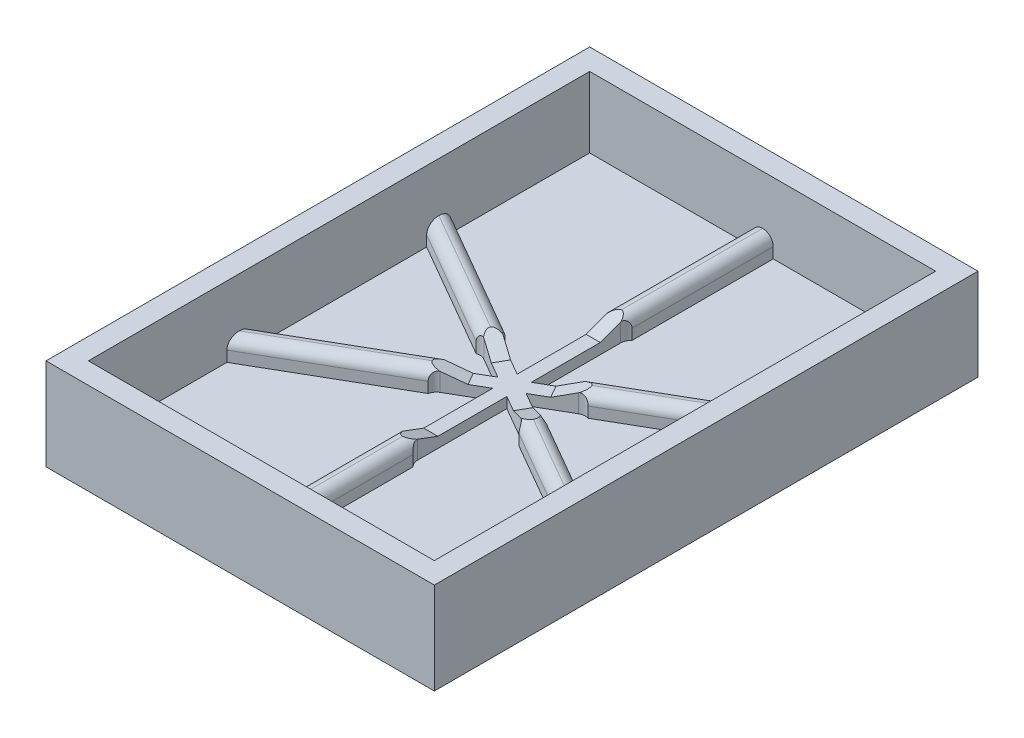
SolidWorks part; units mm, degrees
ref_plane "Plan de face" through (0, 0, 0) normal (0, 0, 1) x (1, 0, 0)
ref_plane "Plan de dessus" through (0, 0, 0) normal (0, 1, 0) x (1, 0, 0)
ref_plane "Plan de droite" through (0, 0, 0) normal (1, 0, 0) x (0, 0, -1)
sketch "Esquisse1" plane through (0, 0, 0) normal (0, 1, 0) x (1, 0, 0)
  line L1 (-27.5, -38.5) -> (27.5, -38.5)
  line L2 (-27.5, -38.5) -> (-27.5, 38.5)
  line L3 (-27.5, 38.5) -> (27.5, 38.5)
  line L4 (27.5, -38.5) -> (27.5, 38.5)
  line L5 (-27.5, -38.5) -> (27.5, 38.5) construction
  line L6 (-27.5, 38.5) -> (27.5, -38.5) construction
  point P0 (0, 0)
  dimension "D1" = 55
  dimension "D2" = 77
extrude "Boss.-Extru.1" add sketch "Esquisse1" along normal blind 3
sketch "Esquisse2" plane through (0, 3, 0) normal (0, 1, 0) x (1, 0, 0)
  line L0 (-24.5, 35.5) -> (-24.5, -35.5)
  line L1 (-27.5, 38.5) -> (27.5, 38.5)
  line L2 (-27.5, 38.5) -> (-27.5, -38.5)
  line L3 (-27.5, -38.5) -> (27.5, -38.5)
  line L4 (27.5, 38.5) -> (27.5, -38.5)
  line L5 (-24.5, -35.5) -> (24.5, -35.5)
  line L6 (24.5, 35.5) -> (24.5, -35.5)
  line L7 (-24.5, 35.5) -> (24.5, 35.5)
  dimension "D1" = 3
extrude "Boss.-Extru.2" add sketch "Esquisse2" along normal blind 10
sketch "Esquisse3" plane through (0, 3, 0) normal (0, 1, 0) x (1, 0, 0)
  line L0 (0, 35.5) -> (0, -35.5) construction
  line L1 (24.5, 35.5) -> (-24.5, 35.5) construction
  line L2 (-24.5, -35.5) -> (24.5, -35.5) construction
  line L3 (-24.5, 14.1451) -> (0, 0) construction
  line L4 (-24.5, 35.5) -> (-24.5, -35.5) construction
  line L5 (0, 0) -> (-24.5, 0) construction
  line L6 (-1, -35.5) -> (-1, -1.7321)
  line L7 (-1, -35.5) -> (1, -35.5)
  line L8 (-1, 35.5) -> (1, 35.5)
  line L9 (1, -35.5) -> (1, -1.7321)
  line L10 (-1, -35.5) -> (1, 35.5) construction
  line L11 (-1, 35.5) -> (1, -35.5) construction
  line L12 (25.4808, -15.866) -> (1, -1.7321)
  line L13 (25.4808, -15.866) -> (26.4808, -14.134)
  line L14 (-26.4808, 14.134) -> (-25.4808, 15.866)
  line L15 (26.4808, -14.134) -> (2, 0)
  line L16 (25.4808, -15.866) -> (-25.4808, 15.866) construction
  line L17 (-26.4808, 14.134) -> (26.4808, -14.134) construction
  line L18 (25.4808, 15.866) -> (26.4808, 14.134)
  line L19 (25.4808, 15.866) -> (1, 1.7321)
  line L20 (26.4808, 14.134) -> (2, 0)
  line L21 (-26.4808, -14.134) -> (-25.4808, -15.866)
  line L22 (-2, 0) -> (-26.4808, -14.134)
  line L23 (-2, 0) -> (-26.4808, 14.134)
  line L24 (-1, -1.7321) -> (-25.4808, -15.866)
  line L25 (-1, 1.7321) -> (-1, 35.5)
  line L26 (-1, 1.7321) -> (-25.4808, 15.866)
  line L27 (1, 1.7321) -> (1, 35.5)
  dimension "D1" = 30
  dimension "D2" = 2
  dimension "D3" = 1
  dimension "D4" = 1
  dimension "D5" = 60
extrude "Boss.-Extru.5" add sketch "Esquisse3" along normal blind 1.5
sketch "Esquisse4" plane through (0, 3, 0) normal (0, 1, 0) x (1, 0, 0)
  line L0 (1, 35.5) -> (-1, 35.5) construction
  line L1 (1.5, 35.5) -> (-1.5, 35.5)
  line L2 (0, 35.5) -> (0, 15.5)
  line L3 (1.5, 15.5) -> (-1.5, 15.5)
  line L4 (-1.5, 35.5) -> (-1.5, 15.5)
  line L5 (1.5, 35.5) -> (1.5, 15.5)
  line L6 (0, 0) -> (24.5, 0) construction
  line L7 (24.5, -35.5) -> (24.5, 35.5) construction
  line L8 (1.5, -35.5) -> (1.5, -15.5)
  line L9 (1.5, -35.5) -> (-1.5, -35.5)
  line L10 (-1.5, -35.5) -> (-1.5, -15.5)
  line L11 (1.5, -15.5) -> (-1.5, -15.5)
  line L12 (-24.5, 14.1451) -> (24.5, -14.1451) construction
  line L13 (-24.5, 15.2998) -> (-24.5, 12.9904) construction
  line L14 (24.5, -15.2998) -> (24.5, -12.9904) construction
  line L15 (24.5, -14.1451) -> (24.5, 14.1451) construction
  line L16 (24.5, 12.9904) -> (24.5, 15.2998) construction
  line L17 (24.5, 14.1451) -> (-24.5, -14.1451) construction
  line L18 (-24.5, -12.9904) -> (-24.5, -15.2998) construction
  line L19 (-24.5, -14.1451) -> (0, 0) construction
  line L20 (0, 0) -> (0, 8.3395) construction
  line L21 (-7.1795, 4.1451) -> (-25.5851, 14.7716)
  line L22 (-7.9295, 2.846) -> (-6.4295, 5.4441)
  line L23 (-26.3351, 13.4725) -> (-24.8351, 16.0706)
  line L24 (-6.4295, 5.4441) -> (-24.8351, 16.0706)
  line L25 (-7.9295, 2.846) -> (-26.3351, 13.4725)
  line L26 (-7.9295, -2.846) -> (-26.3351, -13.4725)
  line L27 (-7.9295, -2.846) -> (-6.4295, -5.4441)
  line L28 (-6.4295, -5.4441) -> (-24.8351, -16.0706)
  line L29 (-26.3351, -13.4725) -> (-24.8351, -16.0706)
  line L30 (7.9295, 2.846) -> (26.3351, 13.4725)
  line L31 (7.9295, 2.846) -> (6.4295, 5.4441)
  line L32 (6.4295, 5.4441) -> (24.8351, 16.0706)
  line L33 (26.3351, 13.4725) -> (24.8351, 16.0706)
  line L34 (7.9295, -2.846) -> (6.4295, -5.4441)
  line L35 (6.4295, -5.4441) -> (24.8351, -16.0706)
  line L36 (26.3351, -13.4725) -> (24.8351, -16.0706)
  line L37 (7.9295, -2.846) -> (26.3351, -13.4725)
  dimension "D1" = 20
  dimension "D2" = 3
  dimension "D3" = 20
  dimension "D4" = 3
extrude "Boss.-Extru.6" add sketch "Esquisse4" along normal blind 3 contours L26 L29 L28 L27 | L5 L3 L4 L1 | L22 L24 L23 L25 | L31 L32 L33 L30 | L35 L36 L37 L34 | L11 L10 L9 L8 region at (-16.3823, 3, 9.4583)
sketch "Esquisse5" plane through (1, 0, 0) normal (1, 0, 0) x (0, 0, -1)
  line L0 (15.5, 4.5) -> (15.5, 6)
  line L1 (15.5, 6) -> (11.5, 4.5)
  line L2 (1.7321, 4.5) -> (15.5, 4.5) construction
  line L3 (11.5, 4.5) -> (15.5, 4.5)
  line L4 (-15.5, 4.5) -> (-15.5, 6)
  line L5 (-15.5, 6) -> (-11.5, 4.5)
  line L6 (-15.5, 4.5) -> (-1.7321, 4.5) construction
  line L7 (-11.5, 4.5) -> (-15.5, 4.5)
  dimension "D1" = 1.5
  dimension "D2" = 4
  dimension "D3" = 4
  dimension "D4" = 1.5
extrude "Boss.-Extru.7" add sketch "Esquisse5" against normal blind 2
sketch "Esquisse6" plane through (0.5, 0, -0.866) normal (0.5, 0, -0.866) x (-0.866, 0, -0.5)
  line L0 (8.2902, 4.5) -> (8.2902, 6)
  line L1 (8.2902, 6) -> (4.2902, 4.5)
  line L2 (1.7321, 4.5) -> (8.2902, 4.5) construction
  line L3 (4.2902, 4.5) -> (8.2902, 4.5)
  line L4 (-8.2902, 4.5) -> (-8.2902, 6)
  line L5 (-8.2902, 6) -> (-4.2902, 4.5)
  line L6 (-8.2902, 4.5) -> (-1.7321, 4.5) construction
  line L7 (-4.2902, 4.5) -> (-8.2902, 4.5)
  dimension "D1" = 4
  dimension "D2" = 1.5
  dimension "D3" = 4
  dimension "D4" = 1.5
extrude "Boss.-Extru.8" add sketch "Esquisse6" against normal blind 2
sketch "Esquisse7" plane through (-0.5, 0, -0.866) normal (-0.5, 0, -0.866) x (-0.866, 0, 0.5)
  line L0 (8.2902, 4.5) -> (8.2902, 6)
  line L1 (8.2902, 6) -> (4.2902, 4.5)
  line L2 (1.7321, 4.5) -> (8.2902, 4.5) construction
  line L3 (4.2902, 4.5) -> (8.2902, 4.5)
  line L4 (-8.2902, 4.5) -> (-8.2902, 6)
  line L5 (-8.2902, 6) -> (-4.2902, 4.5)
  line L6 (-8.2902, 4.5) -> (-1.7321, 4.5) construction
  line L7 (-4.2902, 4.5) -> (-8.2902, 4.5)
  dimension "D1" = 4
  dimension "D2" = 1.5
  dimension "D3" = 4
  dimension "D4" = 1.5
extrude "Boss.-Extru.9" add sketch "Esquisse7" against normal blind 2
fillet "Congé3" radius 1.5 12 edges at (7.6795, 4.5, 3.2791) (6.6795, 4.5, 5.0111) (6.6795, 4.5, -5.0111) (7.6795, 4.5, -3.2791) (-1, 4.5, -15.5) (1, 4.5, -15.5) (-7.6795, 4.5, -3.2791) (-6.6795, 4.5, -5.0111) (1, 4.5, 15.5) (-1, 4.5, 15.5) (-6.6795, 4.5, 5.0111) (-7.6795, 4.5, 3.2791)
fillet "Congé4" radius 1.5 12 edges at (-1.5, 6, -25.5) (1.5, 6, -25.5) (15.4647, 6, -10.6606) (16.2147, 6, -7.6295) (16.2147, 6, 7.6295) (15.4647, 6, 10.6606) (1.5, 6, 25.5) (-1.5, 6, 25.5) (-15.4647, 6, 10.6606) (-16.2147, 6, 7.6295) (-16.2147, 6, -7.6295) (-15.4647, 6, -10.6606)
